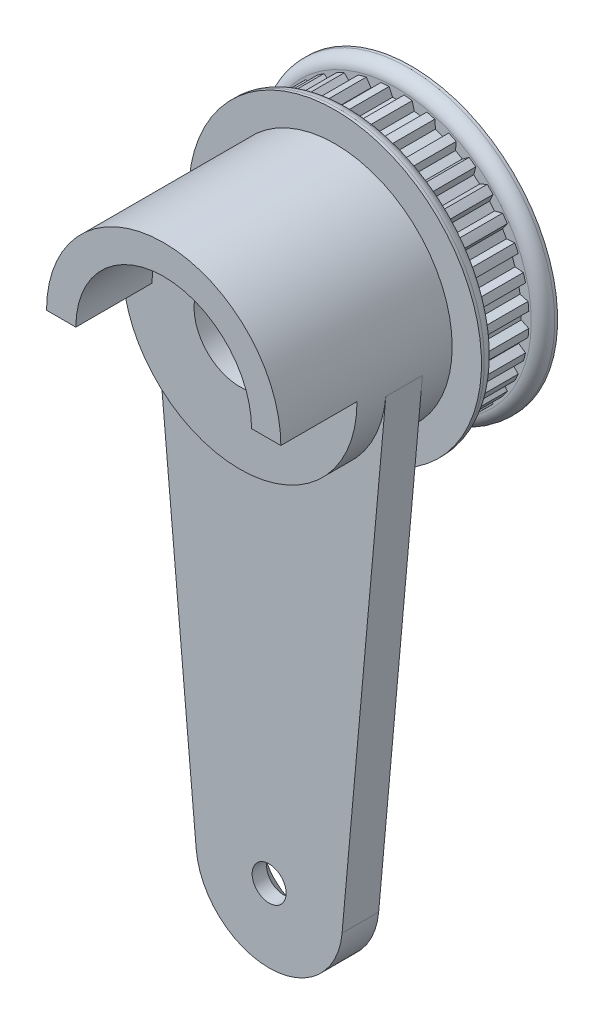
SolidWorks part; units mm, degrees
ref_plane "Front" through (0, 0, 0) normal (0, 0, 1) x (1, 0, 0)
ref_plane "Top" through (0, 0, 0) normal (0, 1, 0) x (1, 0, 0)
ref_plane "Right" through (0, 0, 0) normal (1, 0, 0) x (0, 0, -1)
sketch "Sketch1" plane through (0, 0, 0) normal (0, 0, 1) x (1, 0, 0)
  line L0 (-254, 0) -> (254, 0) construction
  circle A0 centre (0, 0) radius 13.97
  circle A1 centre (0, 0) radius 12.7 construction
  circle A3 centre (0, 0) radius 11.2306 construction
  dimension "D1" = 1.4694
  dimension "D2" = 2.7394
  dimension "D3" = 1.27
extrude "Boss-Extrude1" add sketch "Sketch1" against normal blind 12.7
sketch "Sketch2" plane through (0, 0, 0) normal (1, 0, 0) x (0, 0, -1)
  line L0 (12.7, 0) -> (23.876, 0)
  line L1 (12.7, 0) -> (12.7, 10.668)
  line L2 (12.7, 10.668) -> (23.876, 10.668)
  line L3 (23.876, 10.668) -> (23.876, 0)
  point P5 (23.876, -10.668)
  point P6 (0, -13.97)
  point P7 (12.7, -13.97)
  point P9 (0, 13.97)
revolve "Revolve1" add sketch "Sketch2" angle 360 mid plane about L0 other way angle 360
fillet "Fillet2" radius 0.2794 3 edges at (13.97, 0, -12.7) (13.97, 0, 0) (10.668, 0, -12.7)
sketch "Sketch3" plane through (0, 0, 0) normal (0, 0, 1) x (1, 0, 0)
  line L0 (0, 0) -> (0, 13.97) construction
  line L1 (-4.0817, 11.2144) -> (0, 12.7)
  line L2 (-9.5921, 12.7) -> (9.5921, 12.7) construction
  line L3 (-9.0136, 9.4193) -> (9.0136, 15.9807) construction
  line L4 (-4.0817, 11.2144) -> (0, 0) construction
  line L5 (-9.951, 6.5878) -> (0, 0) construction
  line L6 (-9.951, 6.5878) -> (-3.3571, 16.548) construction
  line L7 (-2.8353, 11.5924) -> (0, 0) construction
  line L8 (-2.8353, 11.5924) -> (0.1182, 12.3148) construction
  arc A0 (-4.0817, 11.2144) -> (-9.951, 6.5878) centre (0, 0) ccw
  circle A1 centre (0, 0) radius 12.7 construction
  circle A2 centre (0, 0) radius 11.9341 construction
  arc A3 (-4.0817, 11.2144) -> (-2.8353, 11.5924) centre (0, 0) cw
  circle A4 centre (0, 0) radius 13.97 construction
  point P6 (0, 12.7)
  dimension "D1" = 4.3437
  dimension "D3" = 11.9451
  dimension "D5" = 3.0406
  dimension "D2" = 7.6014
  dimension "D4" = 1.3031
sketch "Sketch4" plane through (0, 0, 0) normal (0, 0, 1) x (1, 0, 0)
  line L0 (0, 0) -> (0.9934, 12.6218) construction
  line L1 (0.2108, 11.9322) -> (0.2108, 11.2286)
  line L2 (0, 12.7) -> (1.9867, 12.5436) construction
  line L3 (1.6584, 11.8183) -> (1.5483, 11.1234)
  line L4 (0.2108, 11.2286) -> (0, 0) construction
  line L5 (0, 0) -> (0, 13.97) construction
  line L6 (-9.951, 6.5878) -> (-3.3571, 16.548) construction
  line L7 (-9.951, 6.5878) -> (-3.3571, 16.548) construction
  arc A0 (1.5483, 11.1234) -> (0.2108, 11.2286) centre (0, 0) ccw
  arc A1 (0, 12.7) -> (1.9867, 12.5436) centre (0, 0) cw construction
  circle A2 centre (0, 0) radius 12.7 construction
  circle A3 centre (0, 0) radius 11.9341 construction
  circle A4 centre (0, 0) radius 11.2306 construction
  arc A5 (5.9045, 15.8191) -> (-3.3571, 16.548) centre (0, 0) ccw
  spline S0 degree 2 poles (-3.3571, 16.548) (-0.4015, 14.8243) (0.2108, 11.9322) knots 0 0 0 1 1 1
  spline S1 degree 2 poles (5.9045, 15.8191) (2.7156, 14.579) (1.6584, 11.8183) knots 0 0 0 1 1 1
  dimension "D1" = 1.9949
extrude "Cut-Extrude1" cut sketch "Sketch4" against normal through all
fillet "Fillet1" radius 0.5985 2 edges at (1.5483, 11.1234, -6.35) (0.2108, 11.2286, -6.35)
pattern_circular "CirPattern1" count 20 over 360 about axis through (0, 0, -12.7) along (0, 0, 1) of "Cut-Extrude1", "Fillet1"
sketch "Sketch5" plane through (0, 0, 0) normal (0, 0, 1) x (1, 0, 0)
  circle A0 centre (0, 0) radius 6.35
  circle A1 centre (0, 0) radius 6.35 construction
  dimension "Bore Min" = 12.7
  dimension "Bore Max" = 12.7
extrude "Cut-Extrude2" cut sketch "Sketch5" against normal through all
chamfer "Chamfer1" distance 0.5334 angle 45 3 edges at (10.668, 0, -23.876) (6.35, 0, 0) (6.35, 0, -23.876)
sketch "Pitch Dia" plane through (0, 0, 0) normal (0, 0, 1) x (1, 0, 0)
  circle A0 centre (0, 0) radius 12.7 construction
  circle A1 centre (0, 0) radius 12.7 construction
sketch "Sketch7" plane through (0, 0, 0) normal (0, 0, 1) x (1, 0, 0)
  circle A0 centre (0, 0) radius 15.875
  dimension "D1" = 31.75
extrude "Cut-Extrude6" cut sketch "Sketch7" against normal blind 2.54
sketch "Sketch6" plane through (0, 0, -23.876) normal (0, 0, -1) x (-1, 0, 0)
  circle A0 centre (0, 0) radius 15.875
  dimension "D1" = 31.75
extrude "Cut-Extrude7" cut sketch "Sketch6" against normal offset from surface (16.5735 mm away) 4.7625 up to face at (6.35, 0, -2.54)
sketch "Sketch9" plane through (0, 0, -2.54) normal (0, 0, 1) x (1, 0, 0)
  circle A0 centre (0, 0) radius 6.35
  circle A1 centre (0, 0) radius 3.9688
  circle A2 centre (0, 0) radius 6.35 construction
  dimension "D1" = 7.9375
extrude "Boss-Extrude3" add sketch "Sketch9" against normal up to surface (4.7625 mm away) up to face at (6.35, 0, -7.3025)
sketch "Sketch8" plane through (0, 0, -2.54) normal (0, 0, 1) x (1, 0, 0)
  line L0 (10.1192, -0.9099) -> (6.3245, -43.1137)
  line L1 (-6.3245, -43.1137) -> (-10.1192, -0.9099)
  line L2 (0, -42.545) -> (0, 0) construction
  arc A0 (-10.1192, -0.9099) -> (10.1192, -0.9099) centre (0, 0) cw
  arc A1 (6.3245, -43.1137) -> (-6.3245, -43.1137) centre (0, -42.545) cw
  circle A2 centre (0, -42.545) radius 1.4732 construction
  circle A3 centre (0, 0) radius 3.9688
  circle A4 centre (0, 0) radius 3.9688 construction
  dimension "D1" = 10.16
  dimension "D3" = 2.9464
  dimension "D4" = 6.35
  dimension "D2" = 42.545
extrude "Boss-Extrude2" add sketch "Sketch8" along normal blind 3.175
sketch "Sketch10" plane through (0, 0, 0.635) normal (0, 0, 1) x (1, 0, 0)
  circle A0 centre (0, 0) radius 10.16
  circle A1 centre (0, 0) radius 3.9688
  circle A2 centre (0, 0) radius 3.9688 construction
  arc A3 (10.1192, -0.9099) -> (-10.1192, -0.9099) centre (0, 0) ccw construction
extrude "Boss-Extrude4" add sketch "Sketch10" along normal blind 2.54
sketch "Sketch12" plane through (0, 0, 3.175) normal (0, 0, 1) x (1, 0, 0)
  line L0 (-10.16, 0) -> (-7.62, 0)
  line L1 (7.62, 0) -> (10.16, 0)
  arc A0 (-10.16, 0) -> (10.16, 0) centre (0, 0) cw
  circle A2 centre (0, 0) radius 10.16 construction
  arc A3 (10.1192, -0.9099) -> (-10.1192, -0.9099) centre (0, 0) ccw construction
  arc A4 (-7.62, 0) -> (7.62, 0) centre (0, 0) cw
  dimension "D1" = 2.54
extrude "Boss-Extrude5" add sketch "Sketch12" along normal blind 6.604
sketch "Sketch13" plane through (0, 0, -7.3025) normal (0, 0, -1) x (-1, 0, 0)
  circle A0 centre (0, 0) radius 15.875
  dimension "D1" = 31.75
extrude "Cut-Extrude8" cut sketch "Sketch13" against normal up to surface (4.7625 mm away) up to face at (-0.6308, -12.5539, -2.54)
sketch "Sketch18" plane through (0, 0, -2.54) normal (0, 0, -1) x (-1, 0, 0)
  circle A0 centre (0, 0) radius 10.16
  arc A1 (10.1192, -0.9099) -> (-10.1192, -0.9099) centre (0, 0) ccw construction
  circle A2 centre (0, 0) radius 3.9688
  circle A3 centre (0, 0) radius 3.9688 construction
extrude "Boss-Extrude10" add sketch "Sketch18" along normal blind 2.54
sketch "Sketch16" plane through (0, 0, -5.08) normal (0, 0, -1) x (-1, 0, 0)
  circle A0 centre (0, 0) radius 12.7
  circle A1 centre (0, 0) radius 3.9688
  circle A2 centre (0, 0) radius 3.9688 construction
  dimension "D1" = 25.4
extrude "Boss-Extrude8" add sketch "Sketch16" along normal blind 1.27
sketch "Sketch14" plane through (0, 0, -6.35) normal (0, 0, -1) x (-1, 0, 0)
  line L120 (10.5919, 2.2117) -> (10.7096, 1.5443)
  line L121 (11.1831, 2.6256) -> (10.5919, 2.2117)
  line L122 (10.2788, 3.3805) -> (10.9976, 3.3177)
  line L123 (10.047, 4.0174) -> (10.2788, 3.3805)
  line L124 (10.5572, 4.5277) -> (10.047, 4.0174)
  line L125 (9.5356, 5.1141) -> (10.2544, 5.177)
  line L126 (9.1967, 5.701) -> (9.5356, 5.1141)
  line L127 (9.6106, 6.2921) -> (9.1967, 5.701)
  line L128 (8.5027, 6.6922) -> (9.1997, 6.879)
  line L129 (8.067, 7.2114) -> (8.5027, 6.6922)
  line L130 (8.372, 7.8654) -> (8.067, 7.2114)
  line L131 (7.2114, 8.067) -> (7.8654, 8.372)
  line L132 (6.6922, 8.5027) -> (7.2114, 8.067)
  line L133 (6.879, 9.1997) -> (6.6922, 8.5027)
  line L134 (5.701, 9.1967) -> (6.2921, 9.6106)
  line L135 (5.1141, 9.5356) -> (5.701, 9.1967)
  line L136 (5.177, 10.2544) -> (5.1141, 9.5356)
  line L137 (4.0174, 10.047) -> (4.5277, 10.5572)
  line L138 (3.3805, 10.2788) -> (4.0174, 10.047)
  line L139 (3.3177, 10.9976) -> (3.3805, 10.2788)
  line L140 (2.2117, 10.5919) -> (2.6256, 11.1831)
  line L141 (1.5443, 10.7096) -> (2.2117, 10.5919)
  line L142 (1.3575, 11.4067) -> (1.5443, 10.7096)
  line L143 (0.3389, 10.8151) -> (0.6438, 11.4691)
  line L144 (-0.3389, 10.8151) -> (0.3389, 10.8151)
  line L145 (-0.6438, 11.4691) -> (-0.3389, 10.8151)
  line L146 (-1.5443, 10.7096) -> (-1.3575, 11.4067)
  line L147 (-2.2117, 10.5919) -> (-1.5443, 10.7096)
  line L148 (-2.6256, 11.1831) -> (-2.2117, 10.5919)
  line L149 (-3.3805, 10.2788) -> (-3.3177, 10.9976)
  line L150 (-4.0174, 10.047) -> (-3.3805, 10.2788)
  line L151 (-4.5277, 10.5572) -> (-4.0174, 10.047)
  line L152 (-5.1141, 9.5356) -> (-5.177, 10.2544)
  line L153 (-5.701, 9.1967) -> (-5.1141, 9.5356)
  line L154 (-6.2921, 9.6106) -> (-5.701, 9.1967)
  line L155 (-6.6922, 8.5027) -> (-6.879, 9.1997)
  line L156 (-7.2114, 8.067) -> (-6.6922, 8.5027)
  line L157 (-7.8654, 8.372) -> (-7.2114, 8.067)
  line L158 (-8.067, 7.2114) -> (-8.372, 7.8654)
  line L159 (-8.5027, 6.6922) -> (-8.067, 7.2114)
  line L160 (-9.1997, 6.879) -> (-8.5027, 6.6922)
  line L161 (-9.1967, 5.701) -> (-9.6106, 6.2921)
  line L162 (-9.5356, 5.1141) -> (-9.1967, 5.701)
  line L163 (-10.2544, 5.177) -> (-9.5356, 5.1141)
  line L164 (-10.047, 4.0174) -> (-10.5572, 4.5277)
  line L165 (-10.2788, 3.3805) -> (-10.047, 4.0174)
  line L166 (-10.9976, 3.3177) -> (-10.2788, 3.3805)
  line L167 (-10.5919, 2.2117) -> (-11.1831, 2.6256)
  line L168 (-10.7096, 1.5443) -> (-10.5919, 2.2117)
  line L169 (-11.4067, 1.3575) -> (-10.7096, 1.5443)
  line L170 (-10.8151, 0.3389) -> (-11.4691, 0.6438)
  line L171 (-10.8151, -0.3389) -> (-10.8151, 0.3389)
  line L172 (-11.4691, -0.6438) -> (-10.8151, -0.3389)
  line L173 (-10.7096, -1.5443) -> (-11.4067, -1.3575)
  line L174 (-10.5919, -2.2117) -> (-10.7096, -1.5443)
  line L175 (-11.1831, -2.6256) -> (-10.5919, -2.2117)
  line L176 (-10.2788, -3.3805) -> (-10.9976, -3.3177)
  line L177 (-10.047, -4.0174) -> (-10.2788, -3.3805)
  line L178 (-10.5572, -4.5277) -> (-10.047, -4.0174)
  line L179 (-9.5356, -5.1141) -> (-10.2544, -5.177)
  line L180 (-9.1967, -5.701) -> (-9.5356, -5.1141)
  line L181 (-9.6106, -6.2921) -> (-9.1967, -5.701)
  line L182 (-8.5027, -6.6922) -> (-9.1997, -6.879)
  line L183 (-8.067, -7.2114) -> (-8.5027, -6.6922)
  line L184 (-8.372, -7.8654) -> (-8.067, -7.2114)
  line L185 (-7.2114, -8.067) -> (-7.8654, -8.372)
  line L186 (-6.6922, -8.5027) -> (-7.2114, -8.067)
  line L187 (-6.879, -9.1997) -> (-6.6922, -8.5027)
  line L188 (-5.701, -9.1967) -> (-6.2921, -9.6106)
  line L189 (-5.1141, -9.5356) -> (-5.701, -9.1967)
  line L190 (-5.177, -10.2544) -> (-5.1141, -9.5356)
  line L191 (-4.0174, -10.047) -> (-4.5277, -10.5572)
  line L192 (-3.3805, -10.2788) -> (-4.0174, -10.047)
  line L193 (-3.3177, -10.9976) -> (-3.3805, -10.2788)
  line L194 (-2.2117, -10.5919) -> (-2.6256, -11.1831)
  line L195 (-1.5443, -10.7096) -> (-2.2117, -10.5919)
  line L196 (-1.3575, -11.4067) -> (-1.5443, -10.7096)
  line L197 (-0.3389, -10.8151) -> (-0.6438, -11.4691)
  line L198 (0.3389, -10.8151) -> (-0.3389, -10.8151)
  line L199 (0.6438, -11.4691) -> (0.3389, -10.8151)
  line L200 (1.5443, -10.7096) -> (1.3575, -11.4067)
  line L201 (2.2117, -10.5919) -> (1.5443, -10.7096)
  line L202 (2.6256, -11.1831) -> (2.2117, -10.5919)
  line L203 (3.3805, -10.2788) -> (3.3177, -10.9976)
  line L204 (4.0174, -10.047) -> (3.3805, -10.2788)
  line L205 (4.5277, -10.5572) -> (4.0174, -10.047)
  line L206 (5.1141, -9.5356) -> (5.177, -10.2544)
  line L207 (5.701, -9.1967) -> (5.1141, -9.5356)
  line L208 (6.2921, -9.6106) -> (5.701, -9.1967)
  line L209 (6.6922, -8.5027) -> (6.879, -9.1997)
  line L210 (7.2114, -8.067) -> (6.6922, -8.5027)
  line L211 (7.8654, -8.372) -> (7.2114, -8.067)
  line L212 (8.067, -7.2114) -> (8.372, -7.8654)
  line L213 (8.5027, -6.6922) -> (8.067, -7.2114)
  line L214 (9.1997, -6.879) -> (8.5027, -6.6922)
  line L215 (9.1967, -5.701) -> (9.6106, -6.2921)
  line L216 (9.5356, -5.1141) -> (9.1967, -5.701)
  line L217 (10.2544, -5.177) -> (9.5356, -5.1141)
  line L218 (10.047, -4.0174) -> (10.5572, -4.5277)
  line L219 (10.2788, -3.3805) -> (10.047, -4.0174)
  line L220 (10.9976, -3.3177) -> (10.2788, -3.3805)
  line L221 (10.5919, -2.2117) -> (11.1831, -2.6256)
  line L222 (10.7096, -1.5443) -> (10.5919, -2.2117)
  line L223 (11.4067, -1.3575) -> (10.7096, -1.5443)
  line L224 (10.8151, -0.3389) -> (11.4691, -0.6438)
  line L225 (10.8151, 0.3389) -> (10.8151, -0.3389)
  line L226 (11.4691, 0.6438) -> (10.8151, 0.3389)
  line L227 (10.7096, 1.5443) -> (11.4067, 1.3575)
  arc A43 (11.1831, 2.6256) -> (10.9976, 3.3177) centre (0, 0) ccw
  arc A44 (10.5572, 4.5277) -> (10.2544, 5.177) centre (0, 0) ccw
  arc A45 (9.6106, 6.2921) -> (9.1997, 6.879) centre (0, 0) ccw
  arc A46 (8.372, 7.8654) -> (7.8654, 8.372) centre (0, 0) ccw
  arc A47 (6.879, 9.1997) -> (6.2921, 9.6106) centre (0, 0) ccw
  arc A48 (5.177, 10.2544) -> (4.5277, 10.5572) centre (0, 0) ccw
  arc A49 (3.3177, 10.9976) -> (2.6256, 11.1831) centre (0, 0) ccw
  arc A50 (1.3575, 11.4067) -> (0.6438, 11.4691) centre (0, 0) ccw
  arc A51 (-0.6438, 11.4691) -> (-1.3575, 11.4067) centre (0, 0) ccw
  arc A52 (-2.6256, 11.1831) -> (-3.3177, 10.9976) centre (0, 0) ccw
  arc A53 (-4.5277, 10.5572) -> (-5.177, 10.2544) centre (0, 0) ccw
  arc A54 (-6.2921, 9.6106) -> (-6.879, 9.1997) centre (0, 0) ccw
  arc A55 (-7.8654, 8.372) -> (-8.372, 7.8654) centre (0, 0) ccw
  arc A56 (-9.1997, 6.879) -> (-9.6106, 6.2921) centre (0, 0) ccw
  arc A57 (-10.2544, 5.177) -> (-10.5572, 4.5277) centre (0, 0) ccw
  arc A58 (-10.9976, 3.3177) -> (-11.1831, 2.6256) centre (0, 0) ccw
  arc A59 (-11.4067, 1.3575) -> (-11.4691, 0.6438) centre (0, 0) ccw
  arc A60 (-11.4691, -0.6438) -> (-11.4067, -1.3575) centre (0, 0) ccw
  arc A61 (-11.1831, -2.6256) -> (-10.9976, -3.3177) centre (0, 0) ccw
  arc A62 (-10.5572, -4.5277) -> (-10.2544, -5.177) centre (0, 0) ccw
  arc A63 (-9.6106, -6.2921) -> (-9.1997, -6.879) centre (0, 0) ccw
  arc A64 (-8.372, -7.8654) -> (-7.8654, -8.372) centre (0, 0) ccw
  arc A65 (-6.879, -9.1997) -> (-6.2921, -9.6106) centre (0, 0) ccw
  arc A66 (-5.177, -10.2544) -> (-4.5277, -10.5572) centre (0, 0) ccw
  arc A67 (-3.3177, -10.9976) -> (-2.6256, -11.1831) centre (0, 0) ccw
  arc A68 (-1.3575, -11.4067) -> (-0.6438, -11.4691) centre (0, 0) ccw
  arc A69 (0.6438, -11.4691) -> (1.3575, -11.4067) centre (0, 0) ccw
  arc A70 (2.6256, -11.1831) -> (3.3177, -10.9976) centre (0, 0) ccw
  arc A71 (4.5277, -10.5572) -> (5.177, -10.2544) centre (0, 0) ccw
  arc A72 (6.2921, -9.6106) -> (6.879, -9.1997) centre (0, 0) ccw
  arc A73 (7.8654, -8.372) -> (8.372, -7.8654) centre (0, 0) ccw
  arc A74 (9.1997, -6.879) -> (9.6106, -6.2921) centre (0, 0) ccw
  arc A75 (10.2544, -5.177) -> (10.5572, -4.5277) centre (0, 0) ccw
  arc A76 (10.9976, -3.3177) -> (11.1831, -2.6256) centre (0, 0) ccw
  arc A77 (11.4067, -1.3575) -> (11.4691, -0.6438) centre (0, 0) ccw
  arc A78 (11.4691, 0.6438) -> (11.4067, 1.3575) centre (0, 0) ccw
  circle A79 centre (0, 0) radius 3.175 construction
  circle A80 centre (0, 0) radius 3.9688
  circle A81 centre (0, 0) radius 3.9688 construction
extrude "Boss-Extrude6" add sketch "Sketch14" along normal blind 4.064
sketch "Sketch15" plane through (0, 0, -10.414) normal (0, 0, -1) x (-1, 0, 0)
  circle A0 centre (0, 0) radius 3.9688
  circle A1 centre (0, 0) radius 12.7
  circle A3 centre (0, 0) radius 3.9688 construction
  dimension "1" = 25.4
extrude "Boss-Extrude7" add sketch "Sketch15" along normal blind 1.27
fillet "Fillet3" radius 1.016 2 edges at (-12.7, 0, -10.414) (-12.7, 0, -6.35)
hole_wizard "CSK for #4 Flat Head Machine Screw (100)1" positions "Sketch19" profile "Sketch20" countersink size "#4" standard "ANSI Inch" end condition through all
sketch "Sketch19" plane through (0, 0, -2.54) normal (0, 0, -1) x (-1, 0, 0)
  point P0 (0, -42.545)
sketch "Sketch20" plane through (0, -42.545, -2.54) normal (1, 0, 0) x (0, 1, 0)
  line L0 (0, 0) -> (0, 12.319)
  line L1 (0, 12.319) -> (1.4732, 12.319)
  line L2 (1.4732, 12.319) -> (1.4732, 1.9236)
  line L3 (1.4732, 1.9236) -> (3.7656, 0)
  line L5 (3.7656, 0) -> (0, 0)
  line L6 (-1.4732, 1.9236) -> (-3.7656, 0) construction
  line L11 (0, -6.35) -> (0, 107.95) construction
  dimension "Thru Hole Dia." = 2.9464
  dimension "Thru Hole Depth" = 12.319
  dimension "Near C'Sink Dia." = 7.5312
  dimension "Near C'Sink Angle" = 100
equation "\"D1@Boss-Extrude1\" = \"Face Wd@Sketch2\""
equation "\"D2@Sketch3\" = \"D1@Sketch3\"*1.75"
equation "\"D3@Sketch3\" = \"D1@Sketch3\"+\"D2@Sketch3\""
equation "\"D4@Sketch3\" = \"D1@Sketch3\"*.3"
equation "\"D5@Sketch3\" = \"D1@Sketch3\"-\"D4@Sketch3\""
equation "\"D1@Sketch4\" = 1.5708/(\"Number of Teeth@Sketch1\"/\"Ptich Dia@Sketch1\")"
equation "\"D1@Chamfer1\" = \"B Hub Dia@Sketch2\"*.025"
equation "\"D1@CirPattern1\" = \"Number of Teeth@Sketch1\""
equation "\"D1@Fillet1\" = \"D1@Sketch4\"*.3"
equation "\"D1@Fillet2\" = \"OD@Sketch1\"*.01"
equation "\"D1@Sketch1\" = 1.157/(\"Number of Teeth@Sketch1\"/\"Ptich Dia@Sketch1\")"
